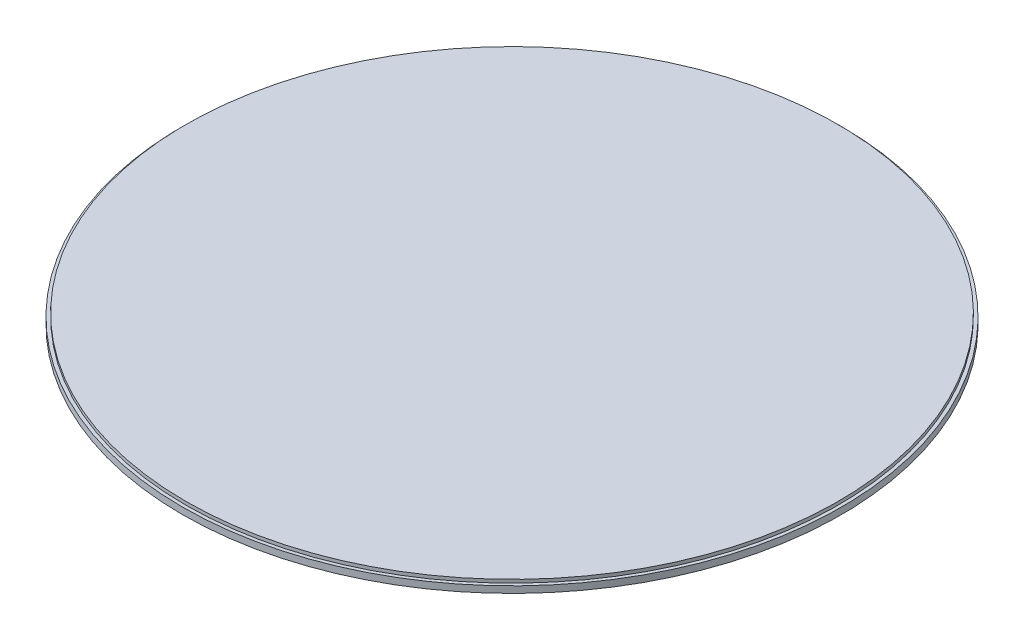
SolidWorks part; units mm, degrees
ref_plane "Front Plane" through (0, 0, 0) normal (0, 0, 1) x (1, 0, 0)
ref_plane "Top Plane" through (0, 0, 0) normal (0, 1, 0) x (1, 0, 0)
ref_plane "Right Plane" through (0, 0, 0) normal (1, 0, 0) x (0, 0, -1)
sketch "Sketch1" plane through (0, 0, 0) normal (0, 1, 0) x (1, 0, 0)
  circle A0 centre (0, 0) radius 100
  circle A1 centre (0, 0) radius 99
  dimension "D1" = 198
  dimension "D2" = 200
extrude "Boss-Extrude1" add sketch "Sketch1" along normal blind 2
extrude "Boss-Extrude2" add sketch "Sketch1<3>" along normal blind 3 contours A1 region at (0, 0, 0)
sketch "Sketch1<3>" plane through (0, 0, 0) normal (0, 1, 0) x (1, 0, 0) same geometry as "Sketch1"
